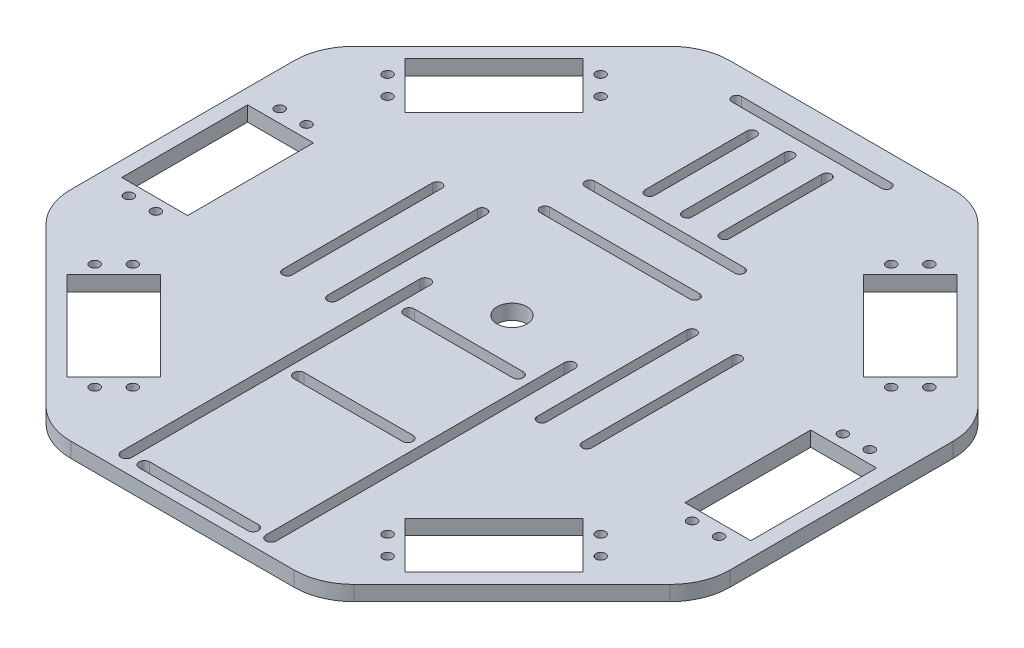
SolidWorks part; units mm, degrees
ref_plane "Front Plane" through (0, 0, 0) normal (0, 0, 1) x (1, 0, 0)
ref_plane "Top Plane" through (0, 0, 0) normal (0, 1, 0) x (1, 0, 0)
ref_plane "Right Plane" through (0, 0, 0) normal (1, 0, 0) x (0, 0, -1)
sketch "Sketch1" plane through (0, 0, 0) normal (0, 1, 0) x (1, 0, 0)
  line L1 (-110, -45.5635) -> (-45.5635, -110)
  line L2 (-45.5635, -110) -> (45.5635, -110)
  line L3 (45.5635, -110) -> (110, -45.5635)
  line L4 (110, -45.5635) -> (110, 45.5635)
  line L5 (110, 45.5635) -> (45.5635, 110)
  line L6 (45.5635, 110) -> (-45.5635, 110)
  line L7 (-45.5635, 110) -> (-110, 45.5635)
  line L8 (-110, 45.5635) -> (-110, -45.5635)
  line L12 (77.7817, -77.7817) -> (0, 0) construction
  line L21 (-20.4, -34.5422) -> (-34.5422, -20.4)
  line L22 (-20.4, -34.5422) -> (-50.0985, -64.2407)
  line L23 (-50.0985, -64.2407) -> (-64.2407, -50.0985)
  line L24 (-34.5422, -20.4) -> (-64.2407, -50.0985)
  line L25 (-38.85, -10) -> (-38.85, 10)
  line L26 (-38.85, -10) -> (-80.85, -10)
  line L27 (-80.85, -10) -> (-80.85, 10)
  line L28 (-38.85, 10) -> (-80.85, 10)
  line L29 (-34.5422, 20.4) -> (-20.4, 34.5422)
  line L30 (-34.5422, 20.4) -> (-64.2407, 50.0985)
  line L31 (-64.2407, 50.0985) -> (-50.0985, 64.2407)
  line L32 (-20.4, 34.5422) -> (-50.0985, 64.2407)
  line L37 (20.4, 34.5422) -> (34.5422, 20.4)
  line L38 (20.4, 34.5422) -> (50.0985, 64.2407)
  line L39 (50.0985, 64.2407) -> (64.2407, 50.0985)
  line L40 (34.5422, 20.4) -> (64.2407, 50.0985)
  line L41 (38.85, 10) -> (38.85, -10)
  line L42 (38.85, 10) -> (80.85, 10)
  line L43 (80.85, 10) -> (80.85, -10)
  line L44 (38.85, -10) -> (80.85, -10)
  circle A0 centre (0, 0) radius 110 construction
  circle A13 centre (0, 0) radius 110 construction
  circle A14 centre (-27.7186, -21.3546) radius 2.5
  circle A15 centre (-21.3546, -27.7186) radius 2.5
  circle A16 centre (-56.9221, -63.2861) radius 2.5
  circle A17 centre (-63.2861, -56.9221) radius 2.5
  circle A18 centre (0, 0) radius 110 construction
  circle A19 centre (-34.7, 4.5) radius 2.5
  circle A20 centre (-34.7, -4.5) radius 2.5
  circle A21 centre (-85, -4.5) radius 2.5
  circle A22 centre (-85, 4.5) radius 2.5
  circle A23 centre (0, 0) radius 110 construction
  circle A24 centre (-21.3546, 27.7186) radius 2.5
  circle A25 centre (-27.7186, 21.3546) radius 2.5
  circle A26 centre (-63.2861, 56.9221) radius 2.5
  circle A27 centre (-56.9221, 63.2861) radius 2.5
  circle A28 centre (0, 0) radius 110 construction
  circle A33 centre (0, 0) radius 110 construction
  circle A34 centre (27.7186, 21.3546) radius 2.5
  circle A35 centre (21.3546, 27.7186) radius 2.5
  circle A36 centre (56.9221, 63.2861) radius 2.5
  circle A37 centre (63.2861, 56.9221) radius 2.5
  circle A38 centre (0, 0) radius 110 construction
  circle A39 centre (34.7, -4.5) radius 2.5
  circle A40 centre (34.7, 4.5) radius 2.5
  circle A41 centre (85, 4.5) radius 2.5
  circle A42 centre (85, -4.5) radius 2.5
  circle A43 centre (0, 0) radius 110 construction
  point P15 (77.7817, -77.7817)
  point P16 (74.2462, -74.2462)
  point P17 (71.3117, -71.3117)
  point P121 (0, 0)
  dimension "D1" = 110
  dimension "D12" = 8
extrude "Baseplate" add sketch "Sketch1" along normal blind 5 contours L7 L8 L1 L2 L3 L4 L5 L6 A42 A41 A40 A39 A37 A36 A35 A34 A27 A26 A25 A24 A22 A21 A20 A19 A17 A16 A15 A14 L44 L41 | L29 L32 L31 L30 | L37 L40 L39 L38 | L41 L44 L43 L42 | L25 L28 L27 L26 | A27 | A26 | A25 | A24 | A22 | A21 | A19 | A20 | A14 | A15 | A17 | A16 | A40 | A41 | A42 | A35 | A34 | A39 | A37 | A36 | L21 L24 L23 L22 region at (1.0949, 0, 1.0949) region at (-59.85, 0, 0) region at (-42.3203, 0, -42.3203) region at (42.3203, 0, -42.3203) region at (59.85, 0, 0) region at (-27.7186, 0, 21.3546) region at (-21.3546, 0, 27.7186) region at (-56.9221, 0, 63.2861) region at (-63.2861, 0, 56.9221) region at (-34.7, 0, -4.5) region at (-34.7, 0, 4.5) region at (-85, 0, 4.5) region at (-85, 0, -4.5) region at (-21.3546, 0, -27.7186) region at (-27.7186, 0, -21.3546) region at (-63.2861, 0, -56.9221) region at (-56.9221, 0, -63.2861) region at (34.7, 0, -4.5) region at (85, 0, -4.5) region at (85, 0, 4.5)
fillet "Fillet1" radius 20 8 edges at (-110, 2.5, -45.5635) (-45.5635, 2.5, -110) (45.5635, 2.5, -110) (110, 2.5, -45.5635) (110, 2.5, 45.5635) (45.5635, 2.5, 110) (-45.5635, 2.5, 110) (-110, 2.5, 45.5635)
sketch "Sketch2" plane through (0, 5, 0) normal (0, 1, 0) x (1, 0, 0)
  line L0 (110, -37.2792) -> (110, 37.2792) construction
  line L1 (83, 16.7208) -> (105, 16.7208)
  line L2 (83, 16.7208) -> (83, -25.2792)
  line L3 (83, -25.2792) -> (105, -25.2792)
  line L4 (105, 16.7208) -> (105, -25.2792)
  circle A0 centre (98.5, 20.9208) radius 1.6
  circle A1 centre (89.5, 20.9208) radius 1.6
  circle A2 centre (89.5, -29.3792) radius 1.6
  circle A3 centre (98.5, -29.3792) radius 1.6
  point P8 (94, 16.7208)
  dimension "D1" = 3.2
  dimension "D2" = 9
  dimension "D3" = 50.3
  dimension "D4" = 22
  dimension "D5" = 42
  dimension "D6" = 4.2
  dimension "D7" = 4.5
  dimension "D8" = 5
  dimension "D9" = 12
extrude "Servo hole" cut sketch "Sketch2" against normal through all contours A0 | L4 L1 L2 L3 | A2 | A3 | A1 region at (94, 5, 4.2792) region at (98.5, 5, -20.9208) region at (89.5, 5, 29.3792) region at (98.5, 5, 29.3792)
sketch "Sketch3" plane through (0, 5, 0) normal (0, 1, 0) x (1, 0, 0)
  circle A0 centre (0, 0) radius 5
  dimension "D1" = 10
extrude "Center hole" cut sketch "Sketch3" against normal through all
pattern_circular "Servo hole pattern" count 8 over 360 about axis through (0, 5, 0) along (0, 1, 0) skipping 2, 3, 4, 5, 6 of "Servo hole"
ref_plane "Midplane" through (0, 0, 0) normal (1, 0, 0) x (0, 0, -1)
mirror "Mirror1" about plane through (0, 0, 0) normal (1, 0, 0) of "Servo hole pattern", "Servo hole"
sketch "Sketch5" plane through (0, 5, 0) normal (0, 1, 0) x (1, 0, 0)
  line L0 (-25, 36) -> (25, 36) construction
  line L1 (-25, 37.6) -> (25, 37.6)
  line L2 (-25, 34.4) -> (25, 34.4)
  line L3 (-25, 51) -> (25, 51) construction
  line L4 (-25, 52.6) -> (25, 52.6)
  line L5 (-25, 49.4) -> (25, 49.4)
  line L6 (-50, 25) -> (-50, -25) construction
  line L7 (-48.4, 25) -> (-48.4, -25)
  line L8 (-51.6, 25) -> (-51.6, -25)
  line L9 (-35, 25) -> (-35, -25) construction
  line L10 (-33.4, 25) -> (-33.4, -25)
  line L11 (-36.6, 25) -> (-36.6, -25)
  line L12 (35, 25) -> (35, -25) construction
  line L13 (36.6, 25) -> (36.6, -25)
  line L14 (33.4, 25) -> (33.4, -25)
  line L15 (50, 25) -> (50, -25) construction
  line L16 (51.6, 25) -> (51.6, -25)
  line L17 (48.4, 25) -> (48.4, -25)
  line L18 (-25, 100) -> (25, 100) construction
  line L19 (-25, 101.6) -> (25, 101.6)
  line L20 (-25, 98.4) -> (25, 98.4)
  line L21 (-12.5, 92.5) -> (-12.5, 58.5) construction
  line L22 (-10.9, 92.5) -> (-10.9, 58.5)
  line L23 (-14.1, 92.5) -> (-14.1, 58.5)
  line L24 (12.5, 92.5) -> (12.5, 58.5) construction
  line L25 (14.1, 92.5) -> (14.1, 58.5)
  line L26 (10.9, 92.5) -> (10.9, 58.5)
  line L27 (37.2792, 110) -> (-37.2792, 110) construction
  line L28 (0, 92.5) -> (0, 58.5) construction
  line L29 (1.6, 92.5) -> (1.6, 58.5)
  line L30 (-1.6, 92.5) -> (-1.6, 58.5)
  arc A0 (-25, 37.6) -> (-25, 34.4) centre (-25, 36) ccw
  arc A1 (25, 34.4) -> (25, 37.6) centre (25, 36) ccw
  arc A2 (-25, 52.6) -> (-25, 49.4) centre (-25, 51) ccw
  arc A3 (25, 49.4) -> (25, 52.6) centre (25, 51) ccw
  arc A4 (-48.4, 25) -> (-51.6, 25) centre (-50, 25) ccw
  arc A5 (-51.6, -25) -> (-48.4, -25) centre (-50, -25) ccw
  arc A6 (-33.4, 25) -> (-36.6, 25) centre (-35, 25) ccw
  arc A7 (-36.6, -25) -> (-33.4, -25) centre (-35, -25) ccw
  arc A8 (36.6, 25) -> (33.4, 25) centre (35, 25) ccw
  arc A9 (33.4, -25) -> (36.6, -25) centre (35, -25) ccw
  arc A10 (51.6, 25) -> (48.4, 25) centre (50, 25) ccw
  arc A11 (48.4, -25) -> (51.6, -25) centre (50, -25) ccw
  arc A12 (-25, 101.6) -> (-25, 98.4) centre (-25, 100) ccw
  arc A13 (25, 98.4) -> (25, 101.6) centre (25, 100) ccw
  arc A14 (-10.9, 92.5) -> (-14.1, 92.5) centre (-12.5, 92.5) ccw
  arc A15 (-14.1, 58.5) -> (-10.9, 58.5) centre (-12.5, 58.5) ccw
  arc A16 (14.1, 92.5) -> (10.9, 92.5) centre (12.5, 92.5) ccw
  arc A17 (10.9, 58.5) -> (14.1, 58.5) centre (12.5, 58.5) ccw
  arc A18 (1.6, 92.5) -> (-1.6, 92.5) centre (0, 92.5) ccw
  arc A19 (-1.6, 58.5) -> (1.6, 58.5) centre (0, 58.5) ccw
  point P2 (0, 36)
  point P7 (0, 51)
  point P14 (-50, 0)
  point P21 (-35, 0)
  point P28 (35, 0)
  point P35 (50, 0)
  point P42 (0, 100)
  point P48 (-12.5, 75.5)
  point P57 (12.5, 75.5)
  point P64 (0, 75.5)
  dimension "D1" = 1.6
  dimension "D7" = 50
  dimension "D2" = 15
  dimension "D3" = 15
  dimension "D4" = 15
  dimension "D5" = 10
  dimension "D6" = 50
  dimension "D8" = 35
  dimension "D9" = 35
  dimension "D10" = 36
  dimension "D11" = 12.5
  dimension "D12" = 12.5
  dimension "D13" = 7.5
  dimension "D14" = 7.5
extrude "Slits" cut sketch "Sketch5" against normal through all contours L30 A19 L29 A18 | L26 A17 L25 A16 | L5 A3 L4 A2 | L2 A1 L1 A0 | L8 A5 L7 A4 | L11 A7 L10 A6 | L14 A9 L13 A8 | L17 A11 L16 A10 | L19 A13 L20 A12 | L22 A15 L23 A14 region at (0, 5, -36) region at (0, 5, -51) region at (-50, 5, 0) region at (-35, 5, 0) region at (35, 5, 0) region at (50, 5, 0) region at (12.5, 5, -75.5) region at (0, 5, -75.5)
ref_plane "Plane1" through (0, 0, 0) normal (0, 0, 1) x (1, 0, 0)
sketch "Sketch6" plane through (0, 5, 0) normal (0, 1, 0) x (1, 0, 0)
  line L0 (24.15, -4.8551) -> (24.15, -104.5705) construction
  line L1 (25.9, -4.8551) -> (25.9, -104.5705)
  line L2 (22.4, -4.8551) -> (22.4, -104.5705)
  line L3 (-24.15, -104.5705) -> (-24.15, -4.8551) construction
  line L4 (-25.9, -104.5705) -> (-25.9, -4.8551)
  line L5 (-22.4, -104.5705) -> (-22.4, -4.8551)
  line L6 (-37.2792, -110) -> (37.2792, -110) construction
  line L7 (-18.15, -52.9705) -> (18.15, -52.9705) construction
  line L8 (-18.15, -51.2205) -> (18.15, -51.2205)
  line L9 (-18.15, -54.7205) -> (18.15, -54.7205)
  line L10 (-18.15, -104.5705) -> (18.15, -104.5705) construction
  line L11 (-18.15, -102.8205) -> (18.15, -102.8205)
  line L12 (-18.15, -106.3205) -> (18.15, -106.3205)
  line L13 (-18.15, -16.1738) -> (18.15, -16.1738) construction
  line L14 (-18.15, -14.4238) -> (18.15, -14.4238)
  line L15 (-18.15, -17.9238) -> (18.15, -17.9238)
  arc A0 (25.9, -4.8551) -> (22.4, -4.8551) centre (24.15, -4.8551) ccw
  arc A1 (22.4, -104.5705) -> (25.9, -104.5705) centre (24.15, -104.5705) ccw
  arc A2 (-25.9, -104.5705) -> (-22.4, -104.5705) centre (-24.15, -104.5705) ccw
  arc A3 (-22.4, -4.8551) -> (-25.9, -4.8551) centre (-24.15, -4.8551) ccw
  arc A4 (-18.15, -51.2205) -> (-18.15, -54.7205) centre (-18.15, -52.9705) ccw
  arc A5 (18.15, -54.7205) -> (18.15, -51.2205) centre (18.15, -52.9705) ccw
  arc A6 (-18.15, -102.8205) -> (-18.15, -106.3205) centre (-18.15, -104.5705) ccw
  arc A7 (18.15, -106.3205) -> (18.15, -102.8205) centre (18.15, -104.5705) ccw
  arc A8 (-18.15, -14.4238) -> (-18.15, -17.9238) centre (-18.15, -16.1738) ccw
  arc A9 (18.15, -17.9238) -> (18.15, -14.4238) centre (18.15, -16.1738) ccw
  point P2 (24.15, -54.7128)
  point P9 (-24.15, -54.7128)
  point P15 (0, -110)
  point P19 (0, -52.9705)
  point P24 (0, -104.5705)
  point P31 (0, -16.1738)
  point P38 (0, 0)
  point P39 (0, 0)
  dimension "D2" = 1.75
  dimension "D3" = 1.75
  dimension "D7" = 1.75
  dimension "D1" = 1.75
  dimension "D10" = 1.75
  dimension "D4" = 48.3
  dimension "D5" = 24.15
  dimension "D6" = 51.6
  dimension "D8" = 6
  dimension "D9" = 6
extrude "Cut-Extrude1" cut sketch "Sketch6" against normal through all contours L9 A5 L8 A4 | L2 A1 L1 A0 | L15 A9 L14 A8 | L12 A7 L11 A6 | L5 A3 L4 A2 region at (24.15, 5, 54.7128) region at (0, 5, 52.9705) region at (0, 5, 104.5705) region at (0, 5, 16.1738)
